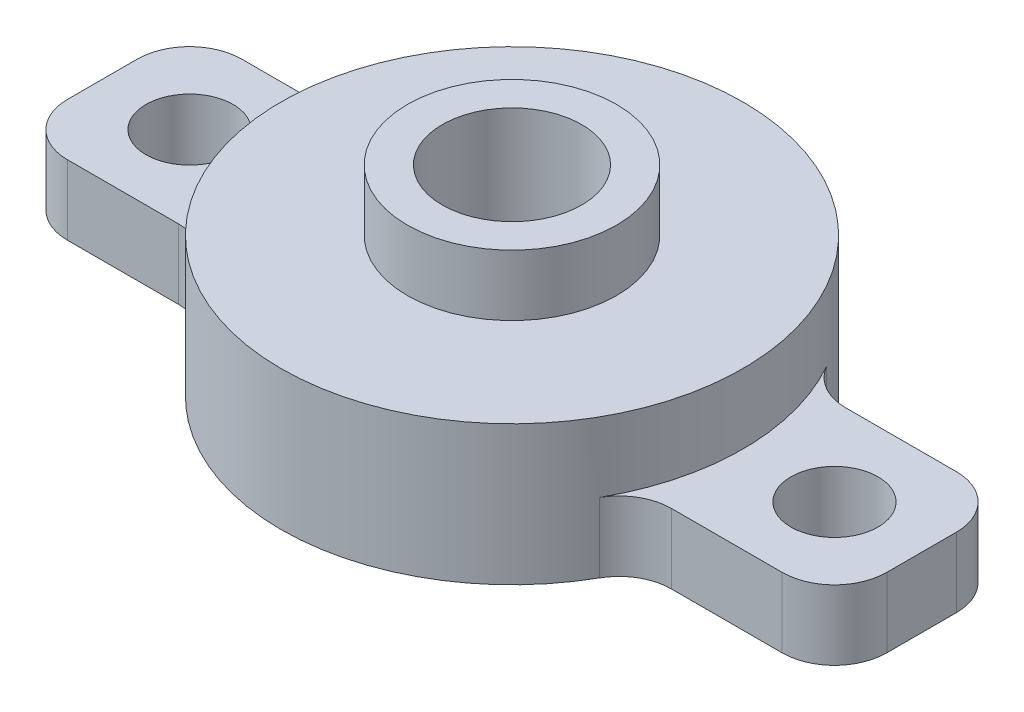
SolidWorks part; units mm, degrees
material "商用纯 CP-Ti UNS R50400 (SS)"
ref_plane "前视基准面" through (0, 0, 0) normal (0, 0, 1) x (1, 0, 0)
ref_plane "上视基准面" through (0, 0, 0) normal (0, 1, 0) x (1, 0, 0)
ref_plane "右视基准面" through (0, 0, 0) normal (1, 0, 0) x (0, 0, -1)
sketch "草图1" plane through (0, 0, 0) normal (0, 1, 0) x (1, 0, 0)
  line L1 (-23.5, 5) -> (-3, 5)
  line L2 (-23.5, 5) -> (-23.5, -5)
  line L3 (-23.5, -5) -> (-3, -5)
  line L4 (-3, 5) -> (-3, -5)
  line L5 (-23.5, 5) -> (-3, -5) construction
  line L6 (-23.5, -5) -> (-3, 5) construction
  line L7 (3, 5) -> (23.5, 5)
  line L8 (3, 5) -> (3, -5)
  line L9 (3, -5) -> (23.5, -5)
  line L10 (23.5, 5) -> (23.5, -5)
  line L11 (3, 5) -> (23.5, -5) construction
  line L12 (3, -5) -> (23.5, 5) construction
  circle A0 centre (0, 0) radius 13.25
  point P3 (-13.25, 0)
  point P8 (13.25, 0)
  dimension "D1" = 26.5
  dimension "D2" = 20.5
  dimension "D3" = 20.5
  dimension "D4" = 10
  dimension "D5" = 10
extrude "凸台-拉伸1" add sketch "草图1" along normal blind 4 contours L1 A0 L3 L4 | A0 L1 L2 L3 | L7 A0 L1 L4 L3 L9 L8 | L9 A0 L7 L8 | A0 L9 L10 L7
sketch "草图2" plane through (0, 4, 0) normal (0, 1, 0) x (1, 0, 0)
  circle A0 centre (0, 0) radius 13.25
extrude "凸台-拉伸2" add sketch "草图2" along normal blind 4
sketch "草图3" plane through (0, 8, 0) normal (0, 1, 0) x (1, 0, 0)
  circle A0 centre (0, 0) radius 6
  dimension "D1" = 12
extrude "凸台-拉伸3" add sketch "草图3" along normal blind 3.5
sketch "草图4" plane through (0, 11.5, 0) normal (0, 1, 0) x (1, 0, 0)
  circle A0 centre (0, 0) radius 4
  dimension "D1" = 8
extrude "切除-拉伸1" cut sketch "草图4" against normal up to next
fillet "圆角1" radius 3 8 edges at (-12.2704, 2, -5) (-12.2704, 2, 5) (12.2704, 2, 5) (12.2704, 2, -5) (23.5, 2, -5) (23.5, 2, 5) (-23.5, 2, -5) (-23.5, 2, 5)
sketch "草图5" plane through (0, 4, 0) normal (0, 1, 0) x (1, 0, 0)
  circle A0 centre (0, 0) radius 18.5
  dimension "D1" = 37
sketch "草图6" plane through (0, 4, 0) normal (0, 1, 0) x (1, 0, 0)
  circle A0 centre (0, 0) radius 18.5 construction
  point P0 (-18.5, 0)
  point P4 (18.5, 0)
hole_wizard "孔1" positions "草图6" profile "草图7" legacy end condition up to next
sketch "草图7" plane through (-18.5, 4, 0) normal (1, 0, 0) x (0, 0, 1)
  line L0 (0, 0) -> (0, 4)
  line L1 (0, 4) -> (2.5, 4)
  line L2 (2.5, 4) -> (2.5, 0)
  line L3 (2.5, 0) -> (0, 0)
  line L4 (0, 110) -> (0, -10) construction
  dimension "直径" = 5
  dimension "深度" = 4
